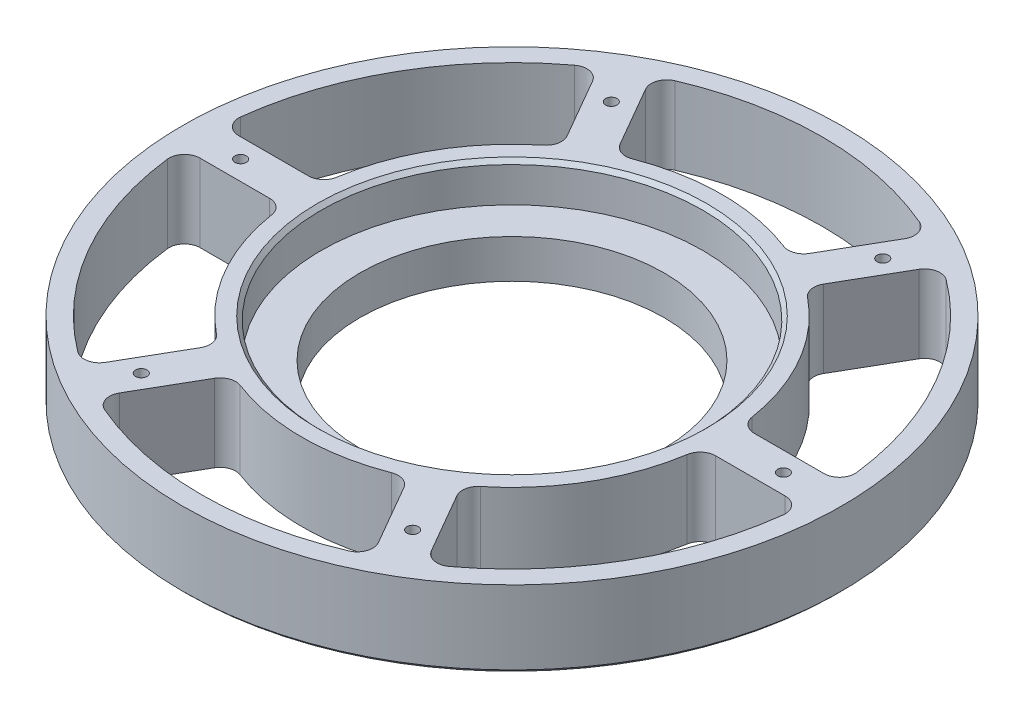
SolidWorks part; units mm, degrees
ref_plane "Front Plane" through (0, 0, 0) normal (0, 0, 1) x (1, 0, 0)
ref_plane "Top Plane" through (0, 0, 0) normal (0, 1, 0) x (1, 0, 0)
ref_plane "Right Plane" through (0, 0, 0) normal (1, 0, 0) x (0, 0, -1)
sketch "Sketch2" plane through (0, 0, 0) normal (1, 0, 0) x (0, 0, -1)
  line L0 (-39.2125, 0) -> (-84.9998, 0)
  line L1 (-84.9998, 0) -> (-84.9998, 20)
  line L2 (-84.9998, 20) -> (-49.2125, 20)
  line L3 (-49.2125, 20) -> (-49.2125, 10)
  line L4 (-49.2125, 10) -> (-39.2125, 10)
  line L5 (-39.2125, 10) -> (-39.2125, 0)
  dimension "D1" = 84.9998
  dimension "D2" = 20
  dimension "D3" = 10
  dimension "D4" = 49.2125
  dimension "D5" = 10
ref_axis "Axis1" through (0, -0.75, 0) along (0, 1, 0)
revolve "Revolve1" add sketch "Sketch2" angle 360 about axis through (0, -0.75, 0) along (0, 1, 0)
hole_wizard "#32 (0.116) Diameter Hole1" positions "Sketch6" profile "Sketch7" hole size "#32" standard "ANSI Inch" end condition through all
sketch "Sketch6" plane through (0, 20, 0) normal (0, 1, 0) x (1, 0, 0)
  line L0 (0, 0) -> (-69.8201, 120.932) construction
  line L2 (0, 0) -> (0, 109.0908) construction
  point P0 (-35, 60.6218)
  dimension "D1" = 30
  dimension "D2" = 70
sketch "Sketch7" plane through (-35, 20, -60.6218) normal (1, 0, 0) x (0, 0, 1)
  line L0 (0, 0) -> (0, 20)
  line L1 (0, 20) -> (1.4732, 20)
  line L2 (1.4732, 20) -> (1.4732, 0)
  line L5 (1.4732, 0) -> (0, 0)
  line L11 (0, -6.35) -> (0, 107.95) construction
  dimension "Thru Hole Dia." = 2.9464
  dimension "Thru Hole Depth" = 20
pattern_circular "CirPattern3" count 6 over 360 about axis through (0, -0.75, 0) along (0, 1, 0) of "#32 (0.116) Diameter Hole1"
sketch "Sketch8" plane through (0, 20, 0) normal (0, 1, 0) x (1, 0, 0)
  line L0 (-35.5916, 71.6464) -> (-22.6606, 49.2493)
  line L1 (35.5916, 71.6464) -> (22.6606, 49.2493)
  line L2 (0, 0) -> (-35, 60.6218) construction
  line L4 (0, 0) -> (0, 93.9995) construction
  arc A0 (-22.6606, 49.2493) -> (22.6606, 49.2493) centre (0, 0) cw
  arc A1 (-35.5916, 71.6464) -> (35.5916, 71.6464) centre (0, 0) cw
  circle A2 centre (0, 0) radius 49.2125 construction
  circle A3 centre (0, 0) radius 84.9998 construction
  point P6 (0, 0)
  dimension "D1" = 5
  dimension "D2" = 5
  dimension "D3" = 5
extrude "Cut-Extrude1" cut sketch "Sketch8" against normal through all
fillet "Fillet1" radius 4 4 edges at (35.5916, 10, -71.6464) (22.6606, 10, -49.2493) (-35.5916, 10, -71.6464) (-22.6606, 10, -49.2493)
pattern_circular "CirPattern4" count 6 over 360 about axis through (0, -0.75, 0) along (0, 1, 0) of "Cut-Extrude1", "Fillet1"
chamfer "Chamfer1" distance 1 angle 45 1 edges at (0, 20, -49.2125)
chamfer "Chamfer2" distance 1 angle 45 1 edges at (0, 0, -84.9998)
